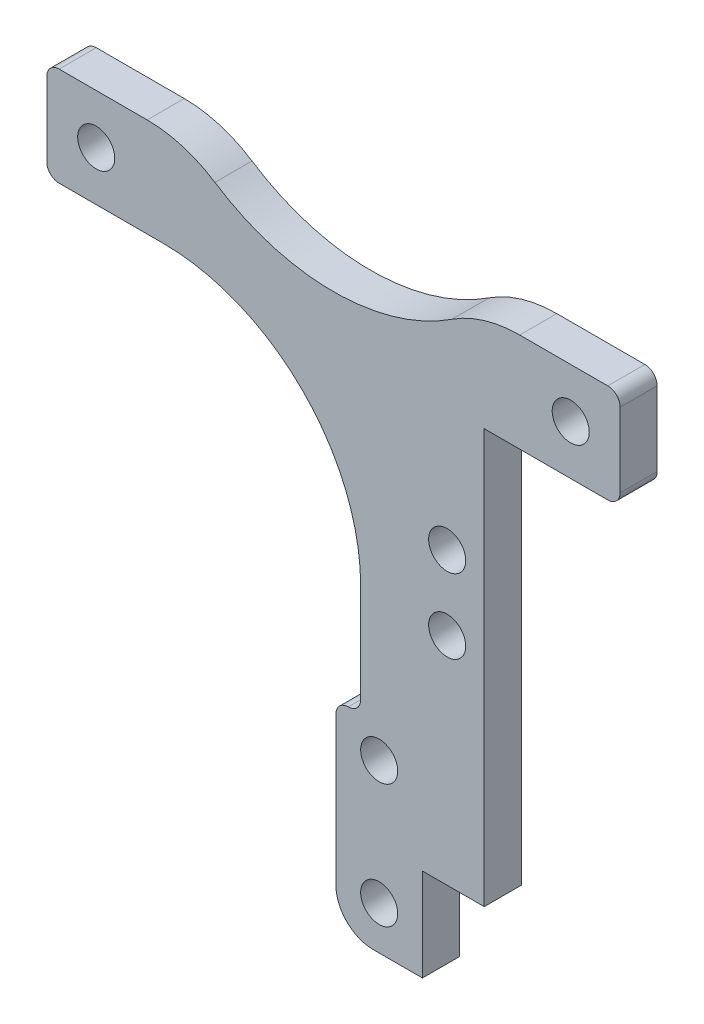
SolidWorks part; units mm, degrees
material "Thornel Mat VMA"
ref_plane "前视基准面" through (0, 0, 0) normal (0, 0, 1) x (1, 0, 0)
ref_plane "上视基准面" through (0, 0, 0) normal (0, 1, 0) x (1, 0, 0)
ref_plane "右视基准面" through (0, 0, 0) normal (1, 0, 0) x (0, 0, -1)
sketch "草图1" plane through (0, 0, 0) normal (0, 0, 1) x (1, 0, 0)
  line L0 (0, 0) -> (0, 3.5)
  line L1 (0, 3.5) -> (-5, 3.5)
  line L2 (-5, 3.5) -> (-5, 13.5)
  line L3 (-5, 13.5) -> (0, 13.5)
  line L4 (0, 13.5) -> (0, 47)
  line L5 (0, 47) -> (11, 47)
  line L6 (11, 47) -> (11, 55)
  line L7 (11, 55) -> (-35.4, 55)
  line L8 (-35.4, 55) -> (-35.4, 47)
  line L9 (0, 0) -> (-10, 0)
  line L11 (-10, 47) -> (-35.4, 47)
  line L12 (-10, 0) -> (-10, 7)
  line L13 (-10, 7) -> (-12, 7)
  line L14 (-12, 7) -> (-12, 22)
  line L15 (-12, 22) -> (-10, 22)
  line L16 (-10, 22) -> (-10, 47)
  line L17 (-31.4, 51) -> (7, 51) construction
  line L18 (-25.4, 55) -> (-25.4, 47) construction
  circle A0 centre (7, 51) radius 1.5
  circle A1 centre (-31.4, 51) radius 1.5
  circle A2 centre (-8.5, 19.5) radius 1.5
  circle A3 centre (-8.5, 9.5) radius 1.5
  dimension "D9" = 3
  dimension "D10" = 7
  dimension "D11" = 4
  dimension "D12" = 3
  dimension "D13" = 38.4
  dimension "D17" = 3
  dimension "D19" = 10
  dimension "D20" = 2.5
  dimension "D21" = 10
  dimension "D1" = 3.5
  dimension "D2" = 5
  dimension "D3" = 10
  dimension "D4" = 33.5
  dimension "D5" = 11
  dimension "D6" = 8
  dimension "D7" = 46.4
  dimension "D8" = 10
  dimension "D14" = 7
  dimension "D15" = 2
  dimension "D16" = 15
  dimension "D18" = 3.5
extrude "凸台-拉伸1" add sketch "草图1" along normal blind 3
fillet "圆角1" radius 1 6 edges at (11, 55, 1.5) (11, 47, 1.5) (-35.4, 47, 1.5) (-35.4, 55, 1.5) (-10, 22, 1.5) (-12, 22, 1.5)
fillet "圆角4" radius 16 1 edges at (-10, 47, 1.5)
sketch "草图2" plane through (0, 0, 3) normal (0, 0, 1) x (1, 0, 0)
  line L0 (-29.9, 51) -> (5.5, 51) construction
  line L1 (-12.2, 51) -> (-12.2, 68) construction
  circle A0 centre (-31.4, 51) radius 1.5 construction
  circle A1 centre (7, 51) radius 1.5 construction
  circle A2 centre (-12.2, 68) radius 17.5
  dimension "D1" = 35
  dimension "D2" = 17
extrude "切除-拉伸1" cut sketch "草图2" against normal blind 3
fillet "圆角5" radius 10 2 edges at (-0.4846, 55, 1.5) (-23.9154, 55, 1.5)
sketch "草图3" plane through (0, 0, 0) normal (0, 0, -1) x (-1, 0, 0)
  line L0 (0, 13.5) -> (0, 47) construction
  line L1 (10, 0) -> (0, 0)
  line L2 (10, 0) -> (10, 7)
  line L3 (10, 7) -> (0, 7)
  line L4 (0, 0) -> (0, 7)
  dimension "D1" = 7
extrude "切除-拉伸2" cut sketch "草图3" against normal blind 10
sketch "草图4" plane through (0, 0, 0) normal (0, 0, -1) x (-1, 0, 0)
  line L0 (12, 21) -> (12, 7) construction
  line L1 (5, 7) -> (12, 7)
  line L2 (5, 7) -> (5, 6)
  line L3 (5, 6) -> (12, 6)
  line L4 (12, 7) -> (12, 6)
  dimension "D1" = 1
extrude "凸台-拉伸2" add sketch "草图4" against normal blind 3
fillet "圆角7" radius 3 1 edges at (-12, 6, 1.5)
sketch "草图5" plane through (0, 0, 3) normal (0, 0, 1) x (1, 0, 0)
  circle A0 centre (-3, 31) radius 1.5
  circle A1 centre (-3, 37) radius 1.5
  dimension "D1" = 3
  dimension "D2" = 3
extrude "切除-拉伸3" cut sketch "草图5" against normal blind 10
